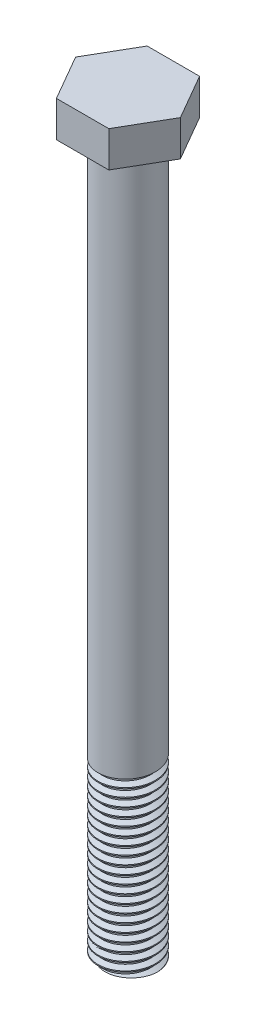
SolidWorks part; units mm, degrees
ref_plane "Front Plane" through (0, 0, 0) normal (0, 0, 1) x (1, 0, 0)
ref_plane "Top Plane" through (0, 0, 0) normal (0, 1, 0) x (1, 0, 0)
ref_plane "Right Plane" through (0, 0, 0) normal (1, 0, 0) x (0, 0, -1)
sketch "Sketch1" plane through (0, 0, 0) normal (0, 1, 0) x (1, 0, 0)
  circle A0 centre (0, 0) radius 6
  dimension "D1" = 12
extrude "Boss-Extrude1" add sketch "Sketch1" against normal blind 150
sketch "Sketch2" plane through (0, 0, 0) normal (0, 1, 0) x (1, 0, 0)
  line L1 (-5.4848, -9.5) -> (5.4848, -9.5)
  line L2 (5.4848, -9.5) -> (10.9697, 0)
  line L3 (10.9697, 0) -> (5.4848, 9.5)
  line L4 (5.4848, 9.5) -> (-5.4848, 9.5)
  line L5 (-5.4848, 9.5) -> (-10.9697, 0)
  line L6 (-10.9697, 0) -> (-5.4848, -9.5)
  circle A0 centre (0, 0) radius 9.5 construction
  dimension "D1" = 19
extrude "Boss-Extrude2" add sketch "Sketch2" along normal blind 7.5
thread "Thread1" pitch 1.75 method cut profile "Thread Profile1" start angle 0, offset 1.75, length 37.75, pitch 1.75, diameter 12
ref_plane "Plane1" through (6, -151.75, 0) normal (0, 0, 1) x (1, 0, 0)
sketch "Thread Profile1" plane through (6, -151.75, 0) normal (0, 0, 1) x (1, 0, 0)
  line L0 (0, 0) -> (0, 1.75) construction
  line L11 (0, 0) -> (0, 1.5312)
  line L12 (0, 1.5312) -> (-0.9472, 0.9844)
  line L13 (-0.9472, 0.9844) -> (-0.9472, 0.5469)
  line L15 (-0.9472, 0.5469) -> (0, 0)
  line L17 (-0.9472, 0.7656) -> (0, 0.7656) construction
  point P2 (0, 0)
  dimension "Pitch" = 1.75
  dimension "Profile_Angle" = 60
  dimension "Profile_Land" = 0.4375
  dimension "Profile_Height" = 0.9472
